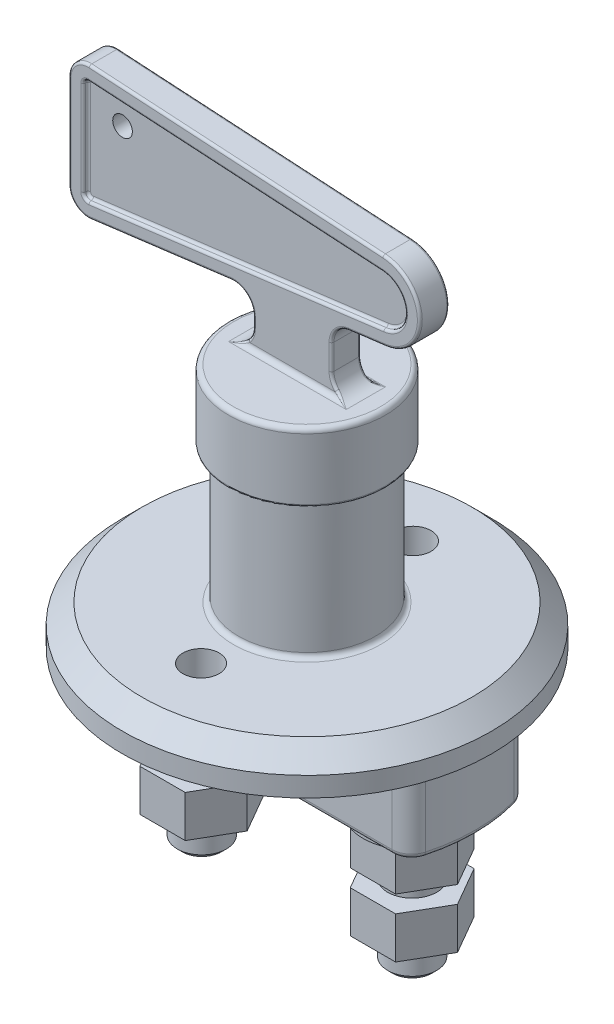
SolidWorks part; units mm, degrees
note: The reader was unsure of these and kept them because the rebuilt part matched: shared geometry of "Sketch7<2>".
ref_plane "Front Plane" through (0, 0, 0) normal (0, 0, 1) x (1, 0, 0)
ref_plane "Top Plane" through (0, 0, 0) normal (0, 1, 0) x (1, 0, 0)
ref_plane "Right Plane" through (0, 0, 0) normal (1, 0, 0) x (0, 0, -1)
sketch "Sketch2" plane through (0, 0, 0) normal (0, 0, 1) x (1, 0, 0)
  line L0 (0, 0) -> (-29.845, 0)
  line L1 (-29.845, 0) -> (-29.845, 3.175)
  line L2 (-29.845, 3.175) -> (-26.67, 6.35)
  line L3 (-26.67, 6.35) -> (-11.1125, 6.35)
  line L4 (-11.1125, 6.35) -> (-11.1125, 38.1)
  line L5 (-11.1125, 38.1) -> (0, 38.1)
  line L6 (0, 38.1) -> (0, 0)
  line L7 (0, 0) -> (0, -35.56) construction
  point P8 (0, 63.6373)
  point P10 (0, 57.4589)
  point P11 (-43.9118, 4.0776)
  dimension "D1" = 73.66
  dimension "D2" = 31.75
  dimension "D3" = 6.35
  dimension "D4" = 45
  dimension "D5" = 3.175
  dimension "D6" = 59.69
  dimension "D7" = 22.225
revolve "Revolve1" add sketch "Sketch2" angle 360 about L7
sketch "Sketch4" plane through (0, 0, 0) normal (0, -1, 0) x (1, 0, 0)
  line L0 (5.7238, -9.525) -> (25.5898, -9.525)
  line L1 (-25.5898, 9.525) -> (-5.7238, 9.525)
  line L3 (-25.5898, -9.525) -> (-5.7238, -9.525)
  line L5 (5.7238, 9.525) -> (25.5898, 9.525)
  arc A1 (25.5898, -9.525) -> (25.5898, 9.525) centre (0, 0) ccw
  circle A2 centre (0, 0) radius 27.305
  arc A3 (-25.5898, 9.525) -> (-25.5898, -9.525) centre (0, 0) ccw
  arc A4 (-5.7238, -9.525) -> (5.7238, -9.525) centre (0, 0) ccw
  arc A5 (5.7238, 9.525) -> (-5.7238, 9.525) centre (0, 0) ccw
  dimension "D1" = 2.54
  dimension "D2" = 22.225
  dimension "D3" = 19.05
extrude "Boss-Extrude2" add sketch "Sketch4" along normal blind 12.7
sketch "Sketch5" plane through (0, 0, 0) normal (0, -1, 0) x (1, 0, 0)
  line L0 (0, 17.145) -> (0, -17.145) construction
  circle A0 centre (0, 17.145) radius 2.921
  circle A1 centre (0, -17.145) radius 2.921
  dimension "D1" = 5.842
  dimension "D2" = 34.29
extrude "Cut-Extrude1" cut sketch "Sketch5" against normal through all
sketch "Sketch8" plane through (0, -12.7, 0) normal (0, -1, 0) x (1, 0, 0)
  circle A0 centre (0, 0) radius 6.35
  dimension "D1" = 12.7
extrude "Boss-Extrude6" add sketch "Sketch8" along normal blind 3.175
fillet "Fillet1" radius 3.175 8 edges at (-5.7238, -6.35, 9.525) (5.7238, -6.35, 9.525) (25.5898, -6.35, 9.525) (25.5898, -6.35, -9.525) (5.7238, -6.35, -9.525) (-5.7238, -6.35, -9.525) (-25.5898, -6.35, 9.525) (-25.5898, -6.35, -9.525)
fillet "Fillet2" radius 0.7937 35 edges at (-25.2066, 0, -8.8732) (-27.305, 0, 0) (-25.2066, 0, 8.8732) (-14.9125, 0, 9.525) (-5.7971, 0, 9.6145) (0, 0, 11.1125) (5.7971, 0, 9.6145) (14.9125, 0, 9.525) (25.2066, 0, 8.8732) (27.305, 0, 0) (25.2066, 0, -8.8732) (14.9125, 0, -9.525) (5.7971, 0, -9.6145) (0, 0, -11.1125) (-5.7971, 0, -9.6145) (6.35, -15.875, 0) (25.2066, -12.7, -8.8732) (14.9125, -12.7, -9.525) (5.7971, -12.7, -9.6145) (0, -12.7, -11.1125) (-5.7971, -12.7, -9.6145) (-14.9125, -12.7, -9.525) (-25.2066, -12.7, -8.8732) (-27.305, -12.7, 0) (-25.2066, -12.7, 8.8732) (-14.9125, -12.7, 9.525) (-5.7971, -12.7, 9.6145) (0, -12.7, 11.1125) (5.7971, -12.7, 9.6145) (14.9125, -12.7, 9.525) (25.2066, -12.7, 8.8732) (27.305, -12.7, 0) (6.35, -12.7, 0) (-14.9125, 0, -9.525) (-11.1125, 6.35, 0)
sketch "Sketch3" plane through (0, 0, 0) normal (0, -1, 0) x (1, 0, 0)
  line L0 (-17.018, 0) -> (17.018, 0) construction
  circle A0 centre (-17.018, 0) radius 3.9688
  circle A1 centre (17.018, 0) radius 3.9688
  dimension "D1" = 7.9375
  dimension "D2" = 34.036
extrude "Boss-Extrude1" add sketch "Sketch3" along normal offset from surface (35.56 mm away) 73.66 up to face at (-11.1125, 38.1, 0)
sketch "Sketch6" plane through (0, -12.7, 0) normal (0, -1, 0) x (1, 0, 0)
  circle A0 centre (17.018, 0) radius 7.9375
  circle A1 centre (-17.018, 0) radius 7.9375
  dimension "D2" = 15.875
extrude "Boss-Extrude3" add sketch "Sketch6" along normal blind 1.5875
sketch "Sketch7" plane through (0, -14.2875, 0) normal (0, -1, 0) x (1, 0, 0)
  line L1 (-13.3518, 6.35) -> (-20.6842, 6.35)
  line L2 (-20.6842, 6.35) -> (-24.3503, 0)
  line L3 (-24.3503, 0) -> (-20.6842, -6.35)
  line L4 (-20.6842, -6.35) -> (-13.3518, -6.35)
  line L5 (-13.3518, -6.35) -> (-9.6857, 0)
  line L6 (-9.6857, 0) -> (-13.3518, 6.35)
  line L7 (13.3518, 6.35) -> (9.6857, 0)
  line L8 (9.6857, 0) -> (13.3518, -6.35)
  line L9 (13.3518, -6.35) -> (20.6842, -6.35)
  line L10 (20.6842, -6.35) -> (24.3503, 0)
  line L11 (24.3503, 0) -> (20.6842, 6.35)
  line L12 (20.6842, 6.35) -> (13.3518, 6.35)
  circle A0 centre (-17.018, 0) radius 6.35 construction
  circle A1 centre (17.018, 0) radius 6.35 construction
  dimension "D1" = 12.7
extrude "Boss-Extrude4" add sketch "Sketch7" along normal blind 6.7469
extrude "Boss-Extrude5" add sketch "Sketch7<2>" along normal blind 6.7469 from offset 9.525
sketch "Sketch7<2>" plane through (0, -14.2875, 0) normal (0, -1, 0) x (1, 0, 0) same geometry as "Sketch7"
chamfer "Chamfer1" distance 0.7937 angle 45 2 edges at (13.0493, -35.56, 0) (-20.9867, -35.56, 0)
sketch "Sketch10" plane through (0, 0, 0) normal (0, 0, 1) x (1, 0, 0)
  line L0 (-36.195, 47.9382) -> (-36.195, 63.1868)
  line L1 (-32.8287, 66.356) -> (14.6702, 63.4885)
  line L2 (15.0879, 50.8507) -> (-32.6198, 44.7885)
  line L3 (14.2875, 57.15) -> (-36.195, 57.15) construction
  line L4 (11.1125, 38.1) -> (-11.1125, 38.1) construction
  line L5 (-29.845, 3.175) -> (-29.845, 0) construction
  line L6 (20.6375, 57.15) -> (20.6375, 6.35) construction
  line L7 (26.67, 6.35) -> (-26.67, 6.35) construction
  line L8 (11.1125, 7.1438) -> (11.1125, 38.1) construction
  arc A0 (14.6702, 63.4885) -> (15.0879, 50.8507) centre (14.2875, 57.15) cw
  arc A1 (-36.195, 47.9382) -> (-32.6198, 44.7885) centre (-33.02, 47.9382) ccw
  arc A2 (-36.195, 63.1868) -> (-32.8287, 66.356) centre (-33.02, 63.1868) cw
  point P5 (-36.195, 55.5625)
  point P13 (-36.195, 44.3342)
  point P22 (-36.195, 66.5592)
  dimension "D1" = 1.5875
  dimension "D3" = 6.35
  dimension "D7" = 3.175
  dimension "D2" = 22.225
  dimension "D4" = 19.05
  dimension "D5" = 6.35
  dimension "D6" = 9.525
extrude "Boss-Extrude7" add sketch "Sketch10" along normal mid plane 4.7625 separate body
sketch "Sketch12" plane through (0, 0, 2.3813) normal (0, 0, 1) x (1, 0, 0)
  line L6 (14.5267, 61.1115) -> (-32.9722, 63.9791)
  line L7 (-33.8137, 63.1868) -> (-33.8137, 47.9382)
  line L8 (-32.9199, 47.1508) -> (14.7878, 53.2129)
  line L9 (14.5267, 61.1115) -> (-32.9722, 63.9791)
  line L10 (-33.8137, 63.1868) -> (-33.8137, 47.9382)
  line L11 (-32.9199, 47.1508) -> (14.7878, 53.2129)
  arc A6 (14.7878, 53.2129) -> (14.5267, 61.1115) centre (14.2875, 57.15) ccw
  arc A7 (-32.9722, 63.9791) -> (-33.8137, 63.1868) centre (-33.02, 63.1868) ccw
  arc A8 (-33.8137, 47.9382) -> (-32.9199, 47.1508) centre (-33.02, 47.9382) ccw
  arc A9 (14.7878, 53.2129) -> (14.5267, 61.1115) centre (14.2875, 57.15) ccw
  arc A10 (-32.9722, 63.9791) -> (-33.8137, 63.1868) centre (-33.02, 63.1868) ccw
  arc A11 (-33.8137, 47.9382) -> (-32.9199, 47.1508) centre (-33.02, 47.9382) ccw
  dimension "D1" = 2.3813
extrude "Cut-Extrude2" cut sketch "Sketch12" against normal blind 0.7937
mirror "Mirror1" about plane through (0, 0, 0) normal (0, 0, 1) of "Cut-Extrude2"
sketch "Sketch14" plane through (0, 0, 0) normal (0, 0, 1) x (1, 0, 0)
  line L0 (-12.7, 28.575) -> (0, 28.575)
  line L2 (0, 39.6875) -> (-12.7, 39.6875)
  line L3 (-12.7, 39.6875) -> (-12.7, 28.575)
  line L4 (0, 39.6875) -> (0, 38.1) construction
  line L5 (11.1125, 38.1) -> (-11.1125, 38.1) construction
  line L6 (0, 39.6875) -> (0, 28.575)
  dimension "D1" = 25.4
  dimension "D2" = 9.525
  dimension "D3" = 1.5875
revolve "Revolve3" add sketch "Sketch14" angle 360 about L4
sketch "Sketch15" plane through (0, 0, 0) normal (0, 0, 1) x (1, 0, 0)
  line L0 (-6.35, 39.6875) -> (-6.35, 48.1266)
  line L1 (12.7, 39.6875) -> (-12.7, 39.6875) construction
  line L2 (-32.6198, 44.7885) -> (15.0879, 50.8507) construction
  line L3 (-6.35, 48.1266) -> (6.35, 49.7403)
  line L4 (6.35, 49.7403) -> (6.35, 39.6875)
  line L5 (6.35, 39.6875) -> (-6.35, 39.6875)
  point P6 (-2.005, 39.6875)
  point P9 (0, 39.6875)
  dimension "D1" = 12.7
extrude "Boss-Extrude8" add sketch "Sketch15" against normal up to surface and the other way up to surface
fillet "Fillet4" radius 3.175 4 edges at (-6.35, 39.6875, 0) (6.35, 39.6875, 0) (6.35, 49.7403, 0) (-6.35, 48.1266, 0)
fillet "Fillet5" radius 0.7937 3 edges at (0, 39.6875, 2.3813) (0, 39.6875, -2.3813) (-12.7, 39.6875, 0)
fillet "Fillet6" radius 0.3969 55 edges at (7.9175, 40.1245, 2.4659) (-7.9175, 40.1245, 2.4659) (-7.9175, 40.1245, -2.4659) (7.9175, 40.1245, -2.4659) (-12.7, 28.575, 0) (-9.0661, 50.1819, 1.5875) (-33.5447, 47.3426, 1.5875) (-33.8137, 55.5625, 1.5875) (-33.5641, 63.7647, 1.5875) (-9.2228, 62.5453, 1.5875) (18.2541, 57.2811, 1.5875) (-6.35, 43.6926, 2.3813) (-7.4262, 46.905, -2.3813) (-7.4262, 46.905, 2.3813) (-21.2725, 46.2304, -2.3813) (-21.2725, 46.2304, 2.3813) (-35.1188, 45.5558, -2.3813) (-35.1188, 45.5558, 2.3813) (-36.195, 55.5625, -2.3813) (-36.195, 55.5625, 2.3813) (-35.1964, 65.4985, -2.3813) (-35.1964, 65.4985, 2.3813) (-9.0793, 64.9222, -2.3813) (-9.0793, 64.9222, 2.3813) (20.634, 57.3598, -2.3813) (20.634, 57.3598, 2.3813) (12.1064, 50.4718, 2.3813) (12.1064, 50.4718, -2.3813) (7.1426, 49.0421, -2.3813) (7.1426, 49.0421, 2.3813) (6.35, 44.9029, 2.3813) (6.6312, 41.5562, 2.3813) (-6.6312, 41.5562, 2.3813) (-33.5641, 63.7647, 2.3813) (-33.8137, 55.5625, 2.3813) (-33.5447, 47.3426, 2.3813) (-9.0661, 50.1819, 2.3813) (18.2541, 57.2811, 2.3813) (-9.2228, 62.5453, 2.3813) (-9.2228, 62.5453, -1.5875) (-33.5641, 63.7647, -1.5875) (-33.8137, 55.5625, -1.5875) (-33.5447, 47.3426, -1.5875) (-9.0661, 50.1819, -1.5875) (18.2541, 57.2811, -1.5875) (-33.5447, 47.3426, -2.3813) (-33.8137, 55.5625, -2.3813) (-33.5641, 63.7647, -2.3813) (-9.2228, 62.5453, -2.3813) (18.2541, 57.2811, -2.3813) (-9.0661, 50.1819, -2.3813) (6.35, 44.9029, -2.3813) (-6.35, 43.6926, -2.3813) (-6.6312, 41.5562, -2.3813) (6.6312, 41.5562, -2.3813)
sketch "Sketch16" plane through (0, 0, -1.5875) normal (0, 0, -1) x (-1, 0, 0)
  line L0 (36.195, 63.1868) -> (36.195, 47.9382) construction
  line L1 (-14.6702, 63.4885) -> (32.8287, 66.356) construction
  circle A0 centre (28.2575, 59.7185) radius 1.5875
  dimension "D1" = 3.175
  dimension "D3" = 6.35
  dimension "D2" = 7.9375
extrude "Cut-Extrude3" cut sketch "Sketch16" against normal through all
